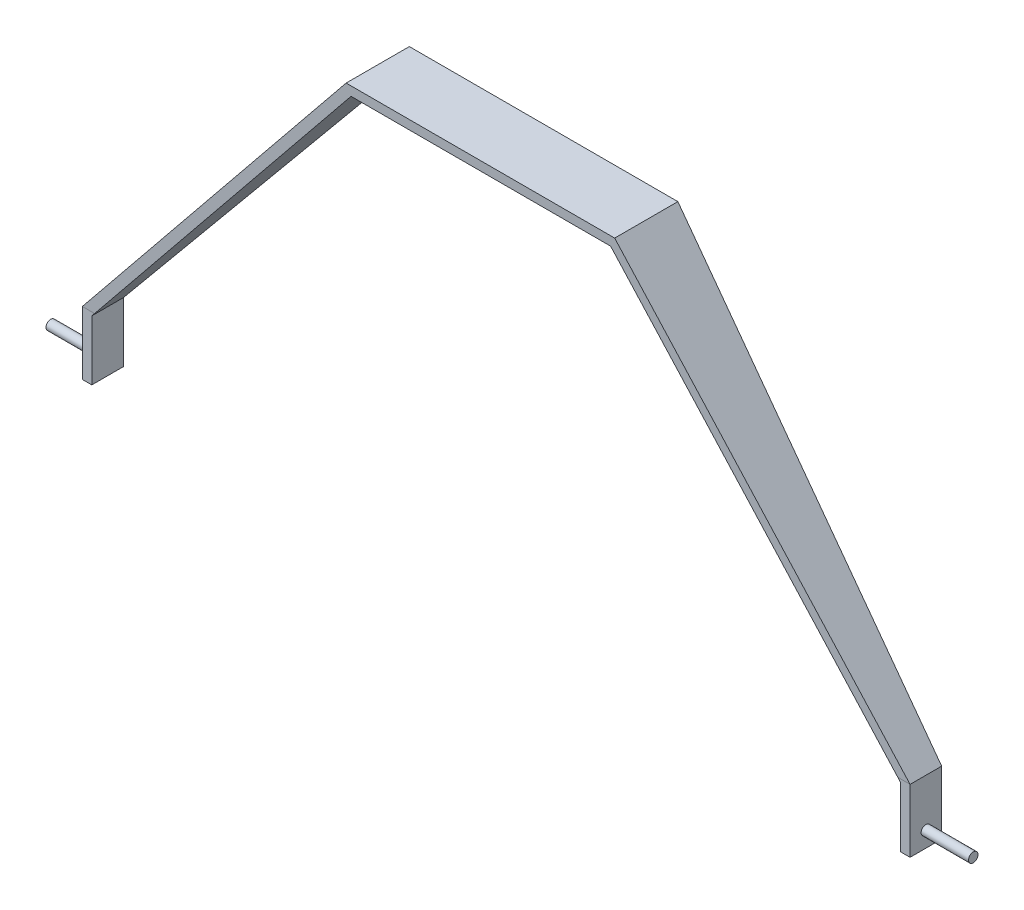
SolidWorks part; units mm, degrees
ref_plane "Front Plane" through (0, 0, 0) normal (0, 0, 1) x (1, 0, 0)
ref_plane "Top Plane" through (0, 0, 0) normal (0, 1, 0) x (1, 0, 0)
ref_plane "Right Plane" through (0, 0, 0) normal (1, 0, 0) x (0, 0, -1)
sketch "Sketch5" plane through (0, 0, 0) normal (0, 0, 1) x (1, 0, 0)
  line L0 (-42.5, 0) -> (42.5, 0)
  line L1 (42.5, 0) -> (131, -108)
  line L2 (131, -108) -> (131, -128)
  line L3 (131, -128) -> (128, -128)
  line L4 (128, -128) -> (128, -109.0722)
  line L5 (128, -109.0722) -> (41.0798, -3)
  line L6 (41.0798, -3) -> (-41.0798, -3)
  line L7 (0, -3) -> (0, 0)
  line L8 (0, 0) -> (0, -158.8716) construction
  line L9 (-128, -109.0722) -> (-41.0798, -3)
  line L10 (-128, -128) -> (-128, -109.0722)
  line L11 (-131, -128) -> (-128, -128)
  line L12 (-131, -108) -> (-131, -128)
  line L13 (-42.5, 0) -> (-131, -108)
  point P4 (131, -118)
  dimension "D1" = 3
  dimension "D2" = 3
  dimension "D3" = 3
  dimension "D4" = 125
  dimension "D5" = 105
  dimension "D6" = 42.5
  dimension "D7" = 128
extrude "Boss-Extrude1" add sketch "Sketch5" along normal blind 20 contours L0 L13 L12 L11 L10 L9 L6 L7 | L7 L6 L5 L4 L3 L2 L1 L0 region at (-21.25, -1.8315, 0) region at (21.25, -1.8315, 0)
sketch "Sketch6" plane through (131, 0, 0) normal (1, 0, 0) x (0, 0, -1)
  line L0 (-15, -128) -> (-15, -108)
  line L1 (-20, -128) -> (0, -128) construction
  line L2 (-20, -108) -> (0, -108) construction
  line L3 (-15, -108) -> (-20, 0)
  line L4 (-20, 0) -> (0, 0)
  line L5 (0, 0) -> (-5, -108)
  line L6 (-5, -108) -> (-5, -128)
  line L7 (-5, -128) -> (-15, -128)
  line L8 (-20, -108) -> (-20, -128) construction
  line L9 (0, -108) -> (0, -128) construction
  line L11 (0, -128) -> (-20, -128)
  line L12 (0, -128) -> (0, 0)
  line L13 (0, 0) -> (-20, 0)
  line L14 (-20, -128) -> (-20, 0)
  line M7 (0, -128) -> (0, -108)
  line M8 (0, -108) -> (-20, -108)
  line M9 (-20, -108) -> (-20, -128)
  line M10 (-20, -128) -> (0, -128)
  dimension "D1" = 5
  dimension "D2" = 5
extrude "Cut-Extrude1" cut sketch "Sketch6" against normal through all contours L0 M10 M8 M9 | L14 L3 M8 | L12 L5 M8 | L6 M8 M10 M7 region at (131, -118, 17.5) region at (131, -72, 18.3333) region at (131, -118, 2.5) region at (131, -72, 1.6667)
sketch "Sketch7" plane through (131, 0, 0) normal (1, 0, 0) x (0, 0, -1)
  line L0 (-15, -128) -> (-5, -128) construction
  line L1 (-5, -108) -> (-5, -128) construction
  circle A0 centre (-10, -123) radius 1.5
  dimension "D1" = 3
  dimension "D2" = 5
  dimension "D3" = 5
extrude "Boss-Extrude2" add sketch "Sketch7" along normal blind 15
sketch "Sketch8" plane through (-131, 0, 0) normal (-1, 0, 0) x (0, 0, 1)
  line L0 (15, -128) -> (5, -128) construction
  line L1 (15, -128) -> (15, -108) construction
  circle A0 centre (10, -123) radius 1.5
  dimension "D1" = 3
  dimension "D2" = 5
  dimension "D3" = 5
extrude "Boss-Extrude3" add sketch "Sketch8" along normal blind 15
